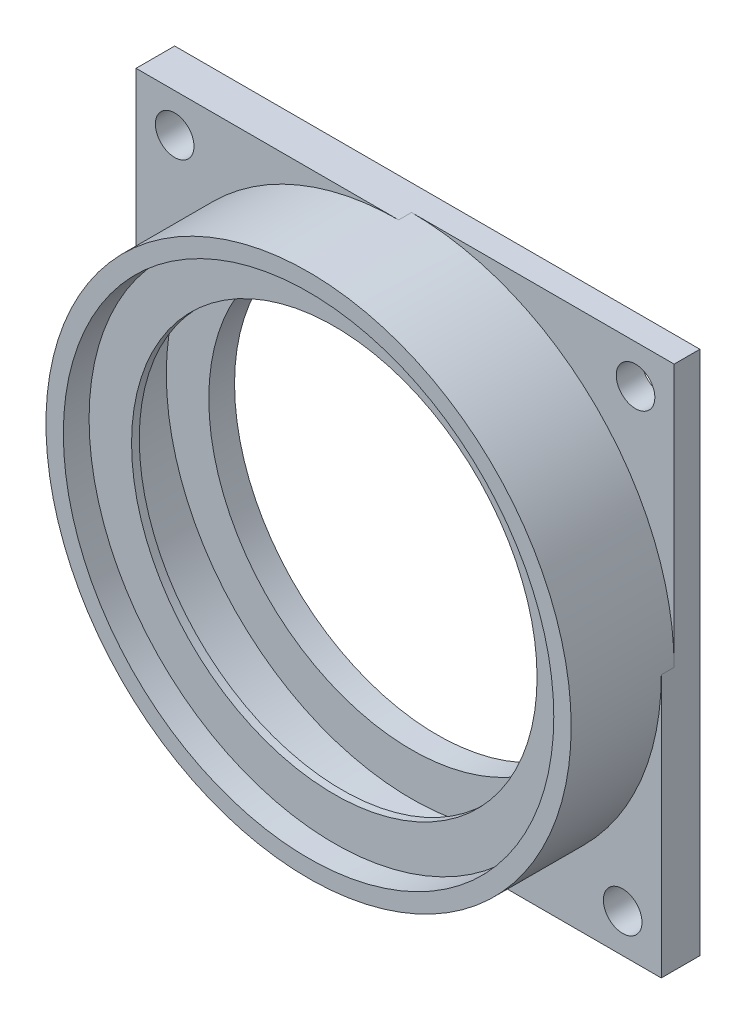
SolidWorks part; units mm, degrees
ref_plane "Front Plane" through (0, 0, 0) normal (0, 0, 1) x (1, 0, 0)
ref_plane "Top Plane" through (0, 0, 0) normal (0, 1, 0) x (1, 0, 0)
ref_plane "Right Plane" through (0, 0, 0) normal (1, 0, 0) x (0, 0, -1)
sketch "Sketch2" plane through (0, 0, 0) normal (0, 0, 1) x (1, 0, 0)
  line L1 (-20.4, -20.4) -> (20.4, -20.4)
  line L2 (-20.4, -20.4) -> (-20.4, 20.4)
  line L3 (-20.4, 20.4) -> (20.4, 20.4)
  line L4 (20.4, -20.4) -> (20.4, 20.4)
  line L5 (-20.4, -20.4) -> (20.4, 20.4) construction
  line L6 (-20.4, 20.4) -> (20.4, -20.4) construction
  circle A0 centre (0, 0) radius 15.75
  circle A1 centre (0, 0) radius 20.4
  circle A2 centre (17.4, 17.4) radius 1.5
  circle A3 centre (17.4, -17.4) radius 1.5
  circle A4 centre (-17.4, -17.4) radius 1.5
  circle A5 centre (-17.4, 17.4) radius 1.5
  point P0 (0, 0)
  point P21 (0, 0)
  dimension "D2" = 31.5
  dimension "D4" = 3
  dimension "D1" = 40.8
  dimension "D3" = 3
  dimension "D5" = 4
extrude "Boss-Extrude1" add sketch "Sketch2" along normal blind 5 contours A1 A0 | A1 L3 L2 A5 | A1 L4 L3 A2 | A1 L1 L4 A3 | A1 L2 L1 A4 region at (-15.7095, -15.7095, 0) region at (15.7095, -15.7095, 0) region at (-14.017, -14.017, 0) region at (-15.7095, 15.7095, 0) region at (15.7095, 15.7095, 0)
extrude "Boss-Extrude2" add sketch "Sketch2<4>" along normal blind 6 from surface contours A1 A0 | A1 L3 L2 A5 | A1 L1 L4 A3 region at (15.7095, -15.7095, 0) region at (-14.017, -14.017, 0) region at (-15.7095, 15.7095, 0) starting at face at (15.75, 0, 5)
sketch "Sketch2<4>" plane through (0, 0, 0) normal (0, 0, 1) x (1, 0, 0) same geometry as "Sketch2"
sketch "Sketch4" plane through (0, 0, 11) normal (0, 0, 1) x (1, 0, 0)
  circle A0 centre (0, 0) radius 15.75 construction
  circle A1 centre (0, 0) radius 15.75
  circle A3 centre (0, 0) radius 19.05
  dimension "D1" = 3.3
extrude "Cut-Extrude2" cut sketch "Sketch4" against normal blind 3 contours A3
sketch "Sketch5" plane through (0, 0, 8) normal (0, 0, 1) x (1, 0, 0)
  circle A0 centre (0, 0) radius 15.75 construction
  circle A1 centre (0, 0) radius 19.05
  circle A2 centre (0, 0) radius 19.05
  circle A3 centre (0, 0) radius 15.75
  dimension "D1" = 0
ref_plane "Plane1" through (0, 0, 2) normal (0, 0, -1) x (-1, 0, 0)
extrude "Cut-Extrude3" cut sketch "Sketch5" along normal offset from surface (5.4 mm away) 0.6 from surface up to face at (15.75, 0, 8) starting at plane "Plane1"
sketch "Sketch6" plane through (0, 0, 5) normal (0, 0, 1) x (1, 0, 0)
  line L2 (20.4, 0) -> (20.4, 20.4)
  line L3 (20.4, 20.4) -> (0, 20.4)
  line L4 (20.4, 0) -> (20.4, 20.4)
  line L5 (20.4, 20.4) -> (0, 20.4)
  line L6 (-20.4, 0) -> (-20.4, -20.4)
  line L7 (-20.4, -20.4) -> (0, -20.4)
  line L8 (-20.4, 0) -> (-20.4, -20.4)
  line L9 (-20.4, -20.4) -> (0, -20.4)
  arc A1 (20.4, 0) -> (0, 20.4) centre (0, 0) ccw
  arc A2 (20.4, 0) -> (0, 20.4) centre (0, 0) ccw
  arc A3 (-20.4, 0) -> (0, -20.4) centre (0, 0) ccw
  arc A4 (-20.4, 0) -> (0, -20.4) centre (0, 0) ccw
  dimension "D1" = 0
  dimension "D2" = 0
extrude "Cut-Extrude4" cut sketch "Sketch6" against normal blind 3
sketch "Sketch7" plane through (0, 0, 11) normal (0, 0, 1) x (1, 0, 0)
  line L8 (20.4, -20.4) -> (20.4, 0)
  line L9 (0, 20.4) -> (-20.4, 20.4)
  line L10 (-20.4, 20.4) -> (-20.4, 0)
  line L11 (0, -20.4) -> (20.4, -20.4)
  line L12 (20.4, -20.4) -> (20.4, 0)
  line L13 (0, 20.4) -> (-20.4, 20.4)
  line L14 (-20.4, 20.4) -> (-20.4, 0)
  line L15 (0, -20.4) -> (20.4, -20.4)
  circle A2 centre (0, 0) radius 19.05 construction
  circle A3 centre (0, 0) radius 19.05
  arc A4 (20.4, 0) -> (0, 20.4) centre (0, 0) ccw
  arc A5 (-20.4, 0) -> (0, -20.4) centre (0, 0) ccw
  arc A6 (20.4, 0) -> (0, 20.4) centre (0, 0) ccw
  arc A7 (-20.4, 0) -> (0, -20.4) centre (0, 0) ccw
  dimension "D1" = 0
extrude "Cut-Extrude5" cut sketch "Sketch7" against normal blind 1
sketch "Sketch8" plane through (0, 0, 8) normal (0, 0, 1) x (1, 0, 0)
  line L4 (0, -20.4) -> (20.4, -20.4)
  line L5 (20.4, -20.4) -> (20.4, 0)
  line L6 (0, 20.4) -> (-20.4, 20.4)
  line L7 (-20.4, 20.4) -> (-20.4, 0)
  line L12 (0, -20.4) -> (20.4, -20.4)
  line L13 (20.4, -20.4) -> (20.4, 0)
  line L14 (0, 20.4) -> (-20.4, 20.4)
  line L15 (-20.4, 20.4) -> (-20.4, 0)
  arc A0 (-20.4, 0) -> (0, 20.4) centre (0, 0) cw
  arc A1 (0, -20.4) -> (20.4, 0) centre (0, 0) ccw
  circle A3 centre (0, 0) radius 19.05
  circle A4 centre (0, 0) radius 19.05
  arc A8 (20.4, 0) -> (0, 20.4) centre (0, 0) ccw
  arc A9 (-20.4, 0) -> (0, -20.4) centre (0, 0) ccw
  arc A10 (20.4, 0) -> (0, 20.4) centre (0, 0) ccw
  arc A11 (-20.4, 0) -> (0, -20.4) centre (0, 0) ccw
  dimension "D1" = 0
  dimension "D2" = 0
extrude "Cut-Extrude6" cut sketch "Sketch8" against normal blind 5 and the other way through all contours A0 | A1 region at (15.8433, -15.8433, 8) region at (-15.8433, 15.8433, 8)
